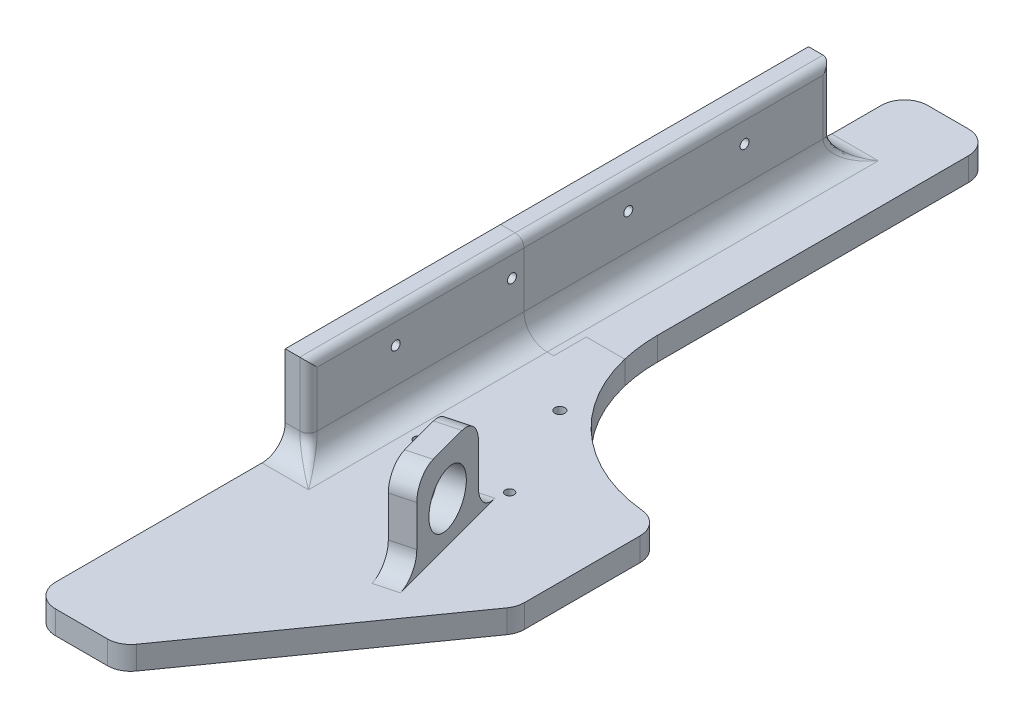
SolidWorks part; units mm, degrees
ref_plane "Front Plane" through (0, 0, 0) normal (0, 0, 1) x (1, 0, 0)
ref_plane "Top Plane" through (0, 0, 0) normal (0, 1, 0) x (1, 0, 0)
ref_plane "Right Plane" through (0, 0, 0) normal (1, 0, 0) x (0, 0, -1)
sketch "Sketch1" plane through (0, 0, 0) normal (0, 1, 0) x (1, 0, 0)
  line L0 (0, 192.4841) -> (-30, 192.4841)
  line L1 (0, -55) -> (0, 55) construction
  line L2 (-30, 192.4841) -> (-30, -107.5159)
  line L3 (-30, -107.5159) -> (0, -107.5159)
  line L4 (0, -107.5159) -> (56.75, -27.5159)
  line L5 (56.75, -27.5159) -> (56.75, 22.4841)
  line L6 (0, 192.4841) -> (0, 77.4562)
  arc A0 (56.75, 22.4841) -> (0, 77.4562) centre (55, 77.4562) cw
  dimension "D2" = 30
  dimension "D3" = 55
  dimension "D1" = 300
  dimension "D4" = 50
  dimension "D5" = 30
  dimension "D6" = 86.75
  dimension "D7" = 80
extrude "Boss-Extrude1" add sketch "Sketch1" along normal blind 8
fillet "Fillet1" radius 8 6 edges at (0, 4, -192.4841) (56.75, 4, -22.4841) (56.75, 4, 27.5159) (-30, 4, 107.5159) (0, 4, 107.5159) (-30, 4, -192.4841)
sketch "Sketch2" plane through (0, 8, 0) normal (0, 1, 0) x (1, 0, 0)
  line L0 (-30, 159.4841) -> (-22, 159.4841)
  line L1 (-30, 184.4841) -> (-30, -99.5159) construction
  line L2 (-22, 159.4841) -> (-22, -20.5159)
  line L3 (-22, -20.5159) -> (-30, -20.5159)
  line L4 (-30, -20.5159) -> (-30, 159.4841)
  arc A0 (-22, 192.4841) -> (-30, 184.4841) centre (-22, 184.4841) ccw construction
  dimension "D1" = 180
  dimension "D2" = 8
  dimension "D3" = 25
extrude "Boss-Extrude2" add sketch "Sketch2" along normal blind 30
sketch "Sketch3" plane through (-22, 0, 0) normal (1, 0, 0) x (0, 0, -1)
  line L0 (-20.5159, 8) -> (159.4841, 8) construction
  line L2 (159.4841, 38) -> (159.4841, 8) construction
  circle A0 centre (9.4841, 28) radius 1.55
  circle A1 centre (49.4841, 28) radius 1.55
  circle A2 centre (89.4841, 28) radius 1.55
  circle A3 centre (129.4841, 28) radius 1.55
  dimension "D1" = 3.1
  dimension "D2" = 40
  dimension "D3" = 40
  dimension "D4" = 40
  dimension "D5" = 20
  dimension "D6" = 30
extrude "Cut-Extrude1" cut sketch "Sketch3" against normal through all
fillet "Fillet2" radius 8 3 edges at (-22, 8, -69.4841) (-26, 8, -159.4841) (-26, 8, 20.5159)
fillet "Fillet3" radius 3 5 edges at (-19.6569, 10.3431, -161.8272) (-19.6569, 10.3431, 22.8591) (-22, 27, -159.4841) (-22, 38, -69.4841) (-22, 27, 20.5159)
sketch "Sketch7" plane through (0, 8, 0) normal (0, 1, 0) x (1, 0, 0)
  circle A0 centre (5.6203, 38.3396) radius 1.7117
  circle A1 centre (21.3703, 5.3018) radius 1.5
  circle A2 centre (-10.1297, 5.3018) radius 1.5
  dimension "D1" = 3
  dimension "D2" = 3
  dimension "D4" = 36.6
  dimension "D3" = 31.5
  dimension "D5" = 15.75
extrude "Cut-Extrude3" cut sketch "Sketch7" against normal up to next
sketch "Sketch5" plane through (0, 8, 0) normal (0, 1, 0) x (1, 0, 0)
  line L0 (22.7, -37.7661) -> (14.9354, -8.7883)
  line L1 (22.7, -37.7661) -> (30.4274, -35.6955)
  line L2 (14.9354, -8.7883) -> (22.6629, -6.7177)
  line L3 (30.4274, -35.6955) -> (22.6629, -6.7177)
  line L4 (22.7, -37.7661) -> (22.6629, -6.7177) construction
  line L5 (14.9354, -8.7883) -> (30.4274, -35.6955) construction
  line L6 (56.75, -24.9666) -> (56.75, 14.767) construction
  point P1 (22.6814, -22.2419)
  dimension "D1" = 8
  dimension "D2" = 30
  dimension "D3" = 15
extrude "Boss-Extrude3" add sketch "Sketch5" along normal blind 30
sketch "Sketch6" plane through (11.7379, 0, -3.1452) normal (-0.9659, 0, 0.2588) x (0.2588, 0, 0.9659)
  line L0 (42.3544, 38) -> (42.3544, 8) construction
  line L1 (19.7797, 8) -> (88.3604, 8) construction
  circle A0 centre (27.3544, 22) radius 9.1
  dimension "D1" = 18.2
  dimension "D2" = 15
  dimension "D3" = 14
extrude "Cut-Extrude2" cut sketch "Sketch6" against normal up to next
fillet "Fillet4" radius 8 4 edges at (18.7991, 8, 7.753) (18.7991, 38, 7.753) (26.5637, 38, 36.7308) (26.5637, 8, 36.7308)
sketch "Sketch4" plane through (0, 38, 0) normal (0, 1, 0) x (1, 0, 0)
  line L0 (-30, 53.5798) -> (-11.7426, 53.5798)
  line L2 (-30, 159.4841) -> (-30, -20.5159) construction
  line L3 (-11.7426, 53.5798) -> (-11.7426, 64.7941)
  line L4 (-11.7426, 64.7941) -> (1.4774, 64.7941)
  arc A1 (0, 77.4562) -> (49.5437, 22.7275) centre (55, 77.4562) ccw construction
split "Split1" trim tools "Sketch4" bodies to split 112 resulting bodies 114 115
